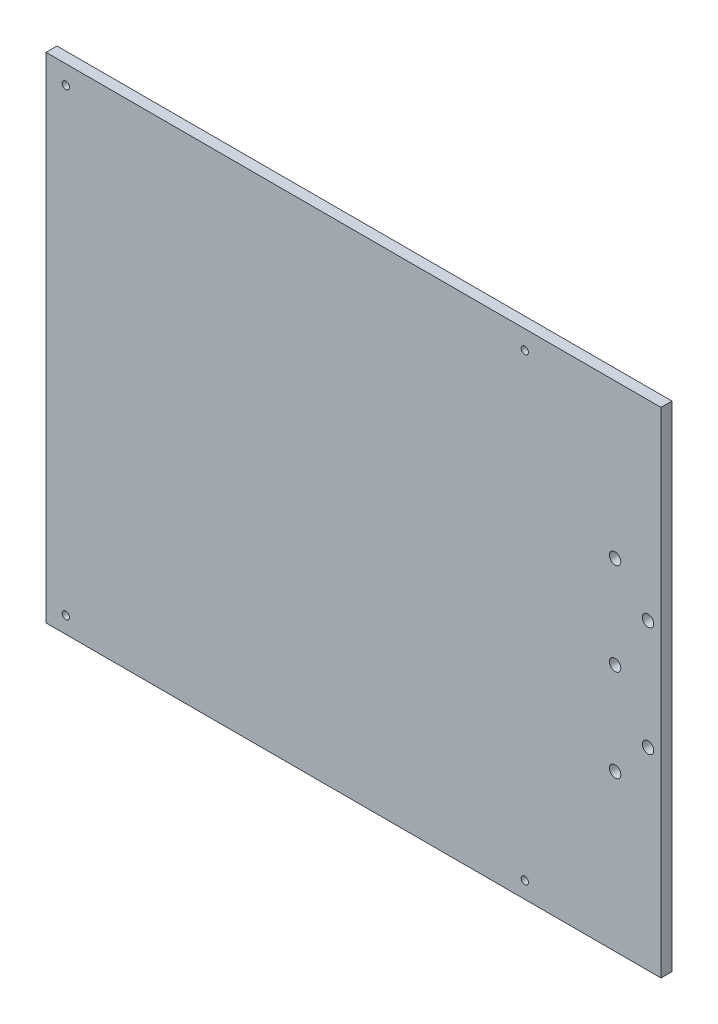
SolidWorks part; units mm, degrees
material "Lega 1060"
ref_plane "Piano frontale" through (0, 0, 0) normal (0, 0, 1) x (1, 0, 0)
ref_plane "Piano superiore" through (0, 0, 0) normal (0, 1, 0) x (1, 0, 0)
ref_plane "Piano destro" through (0, 0, 0) normal (1, 0, 0) x (0, 0, -1)
sketch "Schizzo1" plane through (0, 0, 0) normal (0, 0, 1) x (1, 0, 0)
  line L1 (0, 20) -> (-280, 20)
  line L2 (0, 20) -> (0, 245)
  line L3 (0, 245) -> (-280, 245)
  line L4 (-280, 20) -> (-280, 245)
  dimension "D1" = 280
  dimension "D2" = 225
  dimension "D3" = 20
extrude "Estrusione-Estrusione1" add sketch "Schizzo1" along normal blind 5
hole_wizard "Foro filettato M4-1" positions "Schizzo11" profile "Schizzo10" tap size "M4" standard "ISO" end condition up to next
sketch "Schizzo11" plane through (0, 0, 0) normal (0, 0, -1) x (-1, 0, 0)
  line L0 (280, 20) -> (0, 20) construction
  point P0 (271, 27.5)
  point P2 (62, 27.5)
  point P4 (271, 236.5)
  point P6 (62, 236.5)
  dimension "D1" = 7.5
  dimension "D2" = 209
  dimension "D3" = 209
  dimension "D4" = 9
sketch "Schizzo10" plane through (-271, 27.5, 0) normal (1, 0, 0) x (0, 1, 0)
  line L0 (0, 0) -> (0, 5)
  line L1 (0, 5) -> (1.65, 5)
  line L2 (1.65, 5) -> (1.65, 0)
  line L5 (1.65, 0) -> (0, 0)
  line L11 (0, -6.35) -> (0, 107.95) construction
  dimension "Thru Tap Drill Dia." = 3.3
  dimension "Thru Tap Drill Depth" = 5
cosmetic thread "Filettatura del foro2" parameters "D2"=4
cosmetic thread "Filettatura del foro4" parameters "D2"=4
cosmetic thread "Filettatura del foro5" parameters "D2"=4
cosmetic thread "Filettatura del foro6" parameters "D2"=4
sketch "Schizzo12" plane through (0, 0, 0) normal (0, 0, -1) x (-1, 0, 0)
  circle A0 centre (5.8957, 107.9884) radius 2.6
  circle A1 centre (5.8957, 157.9884) radius 2.6
  circle A2 centre (20.8957, 90.9884) radius 2.6
  circle A3 centre (20.8957, 132.9884) radius 2.6
  circle A4 centre (20.8957, 174.9884) radius 2.6
extrude "Taglio-Estrusione1" cut sketch "Schizzo12" against normal blind 10
